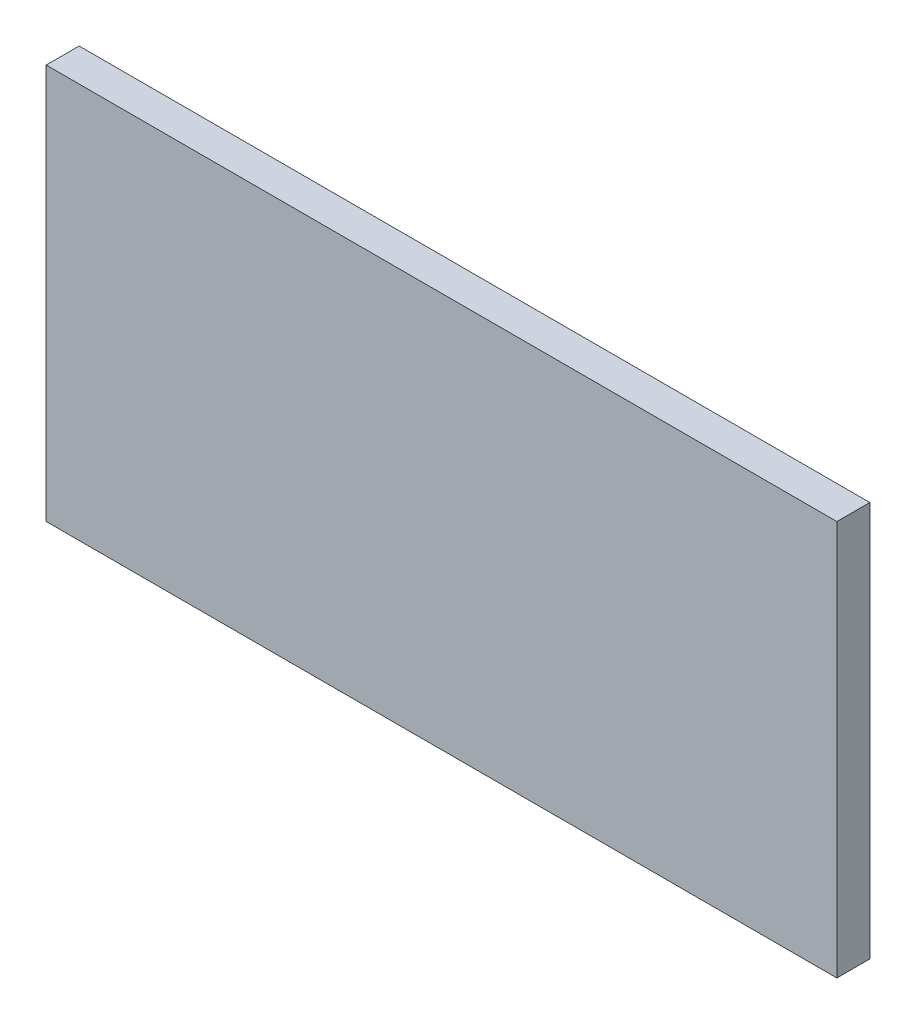
SolidWorks part; units mm, degrees
ref_plane "Front Plane" through (0, 0, 0) normal (0, 0, 1) x (1, 0, 0)
ref_plane "Top Plane" through (0, 0, 0) normal (0, 1, 0) x (1, 0, 0)
ref_plane "Right Plane" through (0, 0, 0) normal (1, 0, 0) x (0, 0, -1)
sketch "Sketch1" plane through (0, 0, 0) normal (0, 0, 1) x (1, 0, 0)
  line L1 (0, 0) -> (152.4, 0)
  line L2 (0, 0) -> (0, -76.2)
  line L3 (0, -76.2) -> (152.4, -76.2)
  line L4 (152.4, 0) -> (152.4, -76.2)
  dimension "D1" = 76.2
  dimension "D2" = 152.4
extrude "Boss-Extrude1" add sketch "Sketch1" along normal blind 6.35
